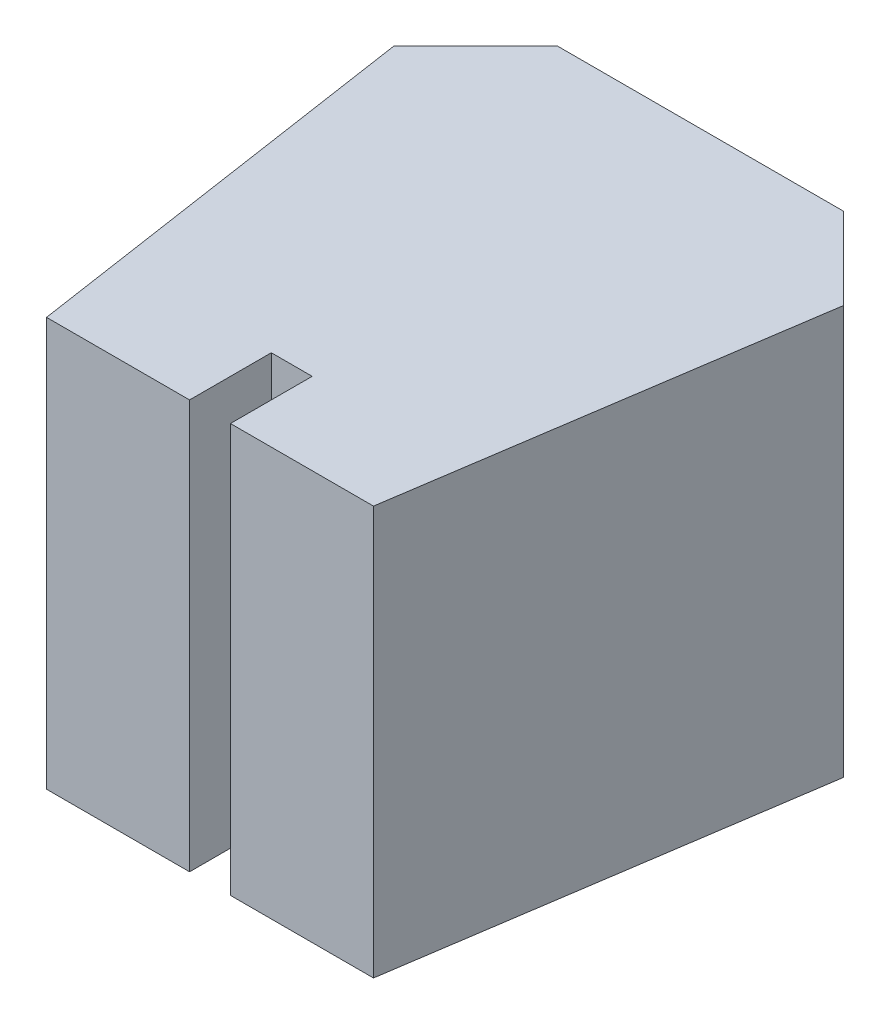
SolidWorks part; units mm, degrees
ref_plane "Front Plane" through (0, 0, 0) normal (0, 0, 1) x (1, 0, 0)
ref_plane "Top Plane" through (0, 0, 0) normal (0, 1, 0) x (1, 0, 0)
ref_plane "Right Plane" through (0, 0, 0) normal (1, 0, 0) x (0, 0, -1)
sketch "Sketch1" plane through (0, 0, 0) normal (0, 1, 0) x (1, 0, 0)
  line L8 (-175, 300) -> (-275, 200)
  line L9 (-175, 300) -> (175, 300)
  line L10 (-275, 300) -> (-275, -300) construction
  line L13 (-200, -300) -> (200, -300)
  line L14 (275, 300) -> (275, -300) construction
  line L15 (175, 300) -> (275, 200)
  line L16 (-275, 200) -> (-200, -300)
  line L17 (275, 200) -> (200, -300)
  line L19 (-25, -300) -> (25, -300)
  line L20 (-25, -300) -> (-25, -200)
  line L21 (-25, -200) -> (25, -200)
  line L22 (25, -300) -> (25, -200)
  dimension "D1" = 550
  dimension "D2" = 600
  dimension "D3" = 275
  dimension "D4" = 300
  dimension "D5" = 100
  dimension "D6" = 100
  dimension "D7" = 75
  dimension "D8" = 75
  dimension "D9" = 50
  dimension "D10" = 100
  dimension "D11" = 25
  dimension "D12" = 100
  dimension "D13" = 100
  dimension "D14" = 400
  dimension "D15" = 500
extrude "Boss-Extrude1" add sketch "Sketch1" along normal blind 500 contours L21 region at (0, 0, -12.9129)
